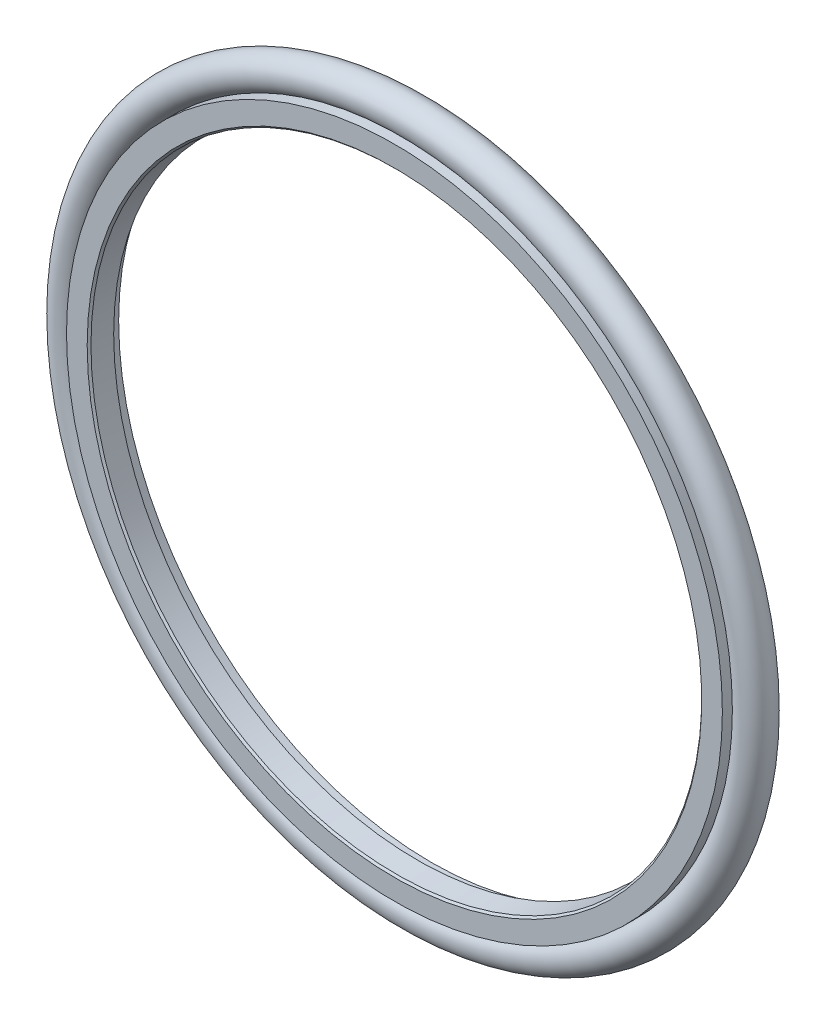
SolidWorks part; units mm, degrees
material "PTFE+NBR"
ref_plane "Front Plane" through (0, 0, 0) normal (0, 0, 1) x (1, 0, 0)
ref_plane "Top Plane" through (0, 0, 0) normal (0, 1, 0) x (1, 0, 0)
ref_plane "Right Plane" through (0, 0, 0) normal (1, 0, 0) x (0, 0, -1)
sketch "Sketch1" plane through (0, 0, 0) normal (1, 0, 0) x (0, 0, -1)
  line L0 (0, 33.3) -> (0, 34.9)
  line L1 (-3.95, 34.9) -> (0, 34.9)
  line L2 (-3.95, 34.9) -> (-3.95, 32.7)
  line L3 (-1.975, 34.9) -> (-1.975, 47.3224) construction
  line L4 (-3.75, 32.5) -> (-1.5, 32.33)
  line L5 (-1.5, 32.33) -> (-0.9, 33.3)
  line L6 (0, 0) -> (-16.4728, 0) construction
  line L7 (0, 33.3) -> (-0.9, 33.3)
  line L8 (-3.75, 32.5) -> (-3.95, 32.7)
  line L9 (-3.95, 34.9) -> (0, 34.9) construction
  point P13 (-0.9, 22.2)
  dimension "D2" = 1.6
  dimension "D4" = 2.4
  dimension "D10" = 1.5
  dimension "D1" = 3.95
  dimension "D3" = 69.8
  dimension "D5" = 2.57
  dimension "D6" = 2.2
  dimension "D7" = 0.9
  dimension "D8" = 0.2
  dimension "D9" = 64.66
  dimension "D11" = 66.6
  dimension "D12" = 65.4
revolve "Revolve1" add sketch "Sketch1" angle 360 about L6
sketch "Sketch4" plane through (0, 0, 0) normal (1, 0, 0) x (0, 0, -1)
  line L0 (0, 0) -> (-3.95, 0) construction
  line L2 (-1.975, 0) -> (-1.975, 52.8756) construction
  line L3 (-3.95, 34.9) -> (-3.95, -34.9) construction
  circle A0 centre (-1.975, 36.485) radius 1.765
  dimension "D1" = 69.44
  dimension "D2" = 3.53
revolve "Revolve2" add sketch "Sketch4" angle 360 about L0
ref_axis "Axis1" through (0, 0, 0) along (0, 0, 1)
